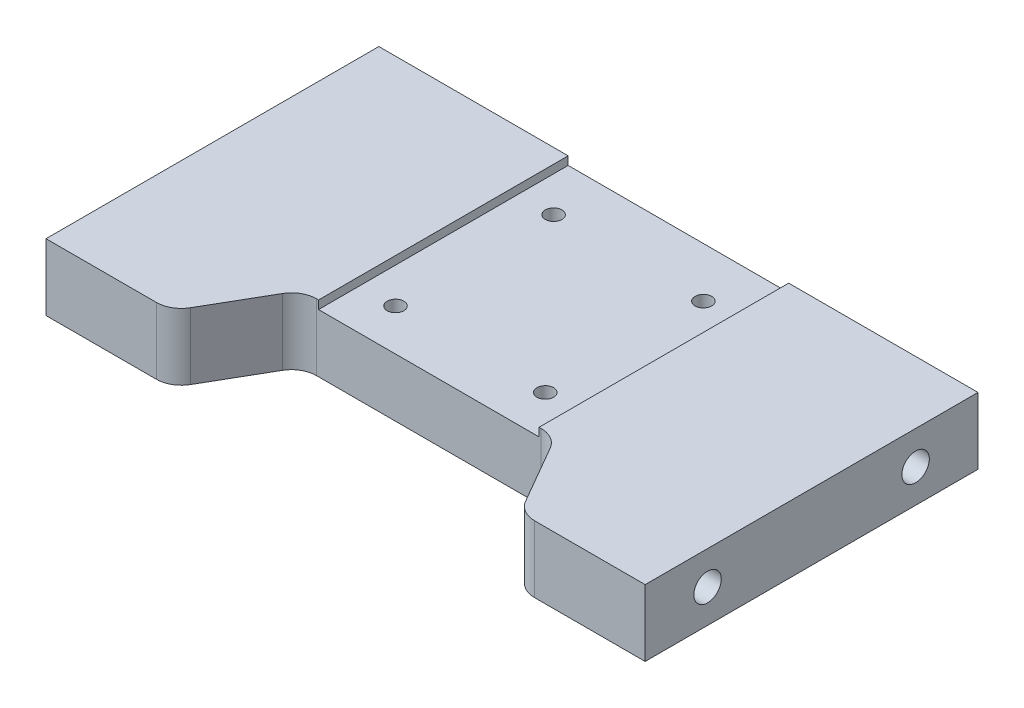
SolidWorks part; units mm, degrees
material "PMMA"
ref_plane "Front Plane" through (0, 0, 0) normal (0, 0, 1) x (1, 0, 0)
ref_plane "Top Plane" through (0, 0, 0) normal (0, 1, 0) x (1, 0, 0)
ref_plane "Right Plane" through (0, 0, 0) normal (1, 0, 0) x (0, 0, -1)
sketch "Sketch1" plane through (0, 0, 0) normal (0, 1, 0) x (1, 0, 0)
  line L1 (0, 0) -> (72, 0)
  line L2 (0, 0) -> (0, 40)
  line L3 (0, 40) -> (72, 40)
  line L4 (72, 0) -> (72, 40)
  dimension "D1" = 72
  dimension "D2" = 40
extrude "Boss-Extrude1" add sketch "Sketch1" along normal blind 8
sketch "Sketch4" plane through (0, 8, 0) normal (0, 1, 0) x (1, 0, 0)
  line L0 (0, 0) -> (72, 0) construction
  line L1 (15, 0) -> (57, 0)
  line L2 (15, 0) -> (20.7735, 10)
  line L3 (20.7735, 10) -> (51.2265, 10)
  line L4 (51.2265, 10) -> (57, 0)
  dimension "D5" = 15
  dimension "D4" = 15
  dimension "D1" = 60
  dimension "D2" = 60
  dimension "D3" = 10
extrude "Cut-Extrude3" cut sketch "Sketch4" against normal up to next
sketch "Sketch5" plane through (0, 8, 0) normal (0, 1, 0) x (1, 0, 0)
  line L0 (51.2265, 10) -> (20.7735, 10) construction
  circle A0 centre (27, 15) radius 1
  circle A1 centre (45, 15) radius 1
  circle A2 centre (45, 34) radius 1
  circle A3 centre (27, 34) radius 1
  dimension "D3" = 2
  dimension "D4" = 5
  dimension "D1" = 18
  dimension "D2" = 19
  dimension "D5" = 27
extrude "Cut-Extrude4" cut sketch "Sketch5" against normal up to next
fillet "Fillet1" radius 3 4 edges at (57, 4, 0) (51.2265, 4, -10) (20.7735, 4, -10) (15, 4, 0)
hole_wizard "Tap Drill for M4 Tap1" positions "Sketch7" profile "Sketch6" hole size "M4" standard "ISO"
sketch "Sketch7" plane through (0, 0, 0) normal (-1, 0, 0) x (0, 0, 1)
  line L0 (0, 8) -> (0, 0) construction
  line L1 (-40, 0) -> (0, 0) construction
  point P0 (-32.5, 4)
  point P2 (-7.5, 4)
  dimension "D1" = 7.5
  dimension "D2" = 25
  dimension "D3" = 4
sketch "Sketch6" plane through (0, 4, -32.5) normal (0, 1, 0) x (0, 0, 1)
  line L0 (0, 0) -> (0, 10.9914)
  line L1 (0, 10.9914) -> (1.65, 10)
  line L2 (1.65, 10) -> (1.65, 0)
  line L5 (1.65, 0) -> (0, 0)
  line L10 (0, 10.9914) -> (-1.65, 10) construction
  line L11 (0, -6.35) -> (0, 107.95) construction
  dimension "Hole Dia." = 3.3
  dimension "Hole Depth" = 10
  dimension "Drill Angle" = 118
hole_wizard "Tap Drill for M4 Tap2" positions "Sketch9" profile "Sketch8" hole size "M4" standard "ISO"
sketch "Sketch9" plane through (72, 0, 0) normal (1, 0, 0) x (0, 0, -1)
  line L0 (0, 8) -> (0, 0) construction
  line L1 (0, 0) -> (40, 0) construction
  point P0 (7.5, 4)
  point P2 (32.5, 4)
  dimension "D1" = 7.5
  dimension "D2" = 25
  dimension "D3" = 4
sketch "Sketch8" plane through (72, 4, -7.5) normal (0, 1, 0) x (0, 0, -1)
  line L0 (0, 0) -> (0, 10.9914)
  line L1 (0, 10.9914) -> (1.65, 10)
  line L2 (1.65, 10) -> (1.65, 0)
  line L5 (1.65, 0) -> (0, 0)
  line L10 (0, 10.9914) -> (-1.65, 10) construction
  line L11 (0, -6.35) -> (0, 107.95) construction
  dimension "Hole Dia." = 3.3
  dimension "Hole Depth" = 10
  dimension "Drill Angle" = 118
sketch "Sketch10" plane through (0, 8, 0) normal (0, 1, 0) x (1, 0, 0)
  line L0 (49.4944, 10) -> (22.5056, 10) construction
  line L1 (22.75, 10) -> (49.25, 10)
  line L2 (22.75, 10) -> (22.75, 40)
  line L3 (22.75, 40) -> (49.25, 40)
  line L4 (49.25, 10) -> (49.25, 40)
  line L6 (72, 40) -> (0, 40) construction
  circle A0 centre (27, 15) radius 1 construction
  dimension "D1" = 26.5
  dimension "D2" = 4.25
extrude "Cut-Extrude5" cut sketch "Sketch10" against normal blind 1
